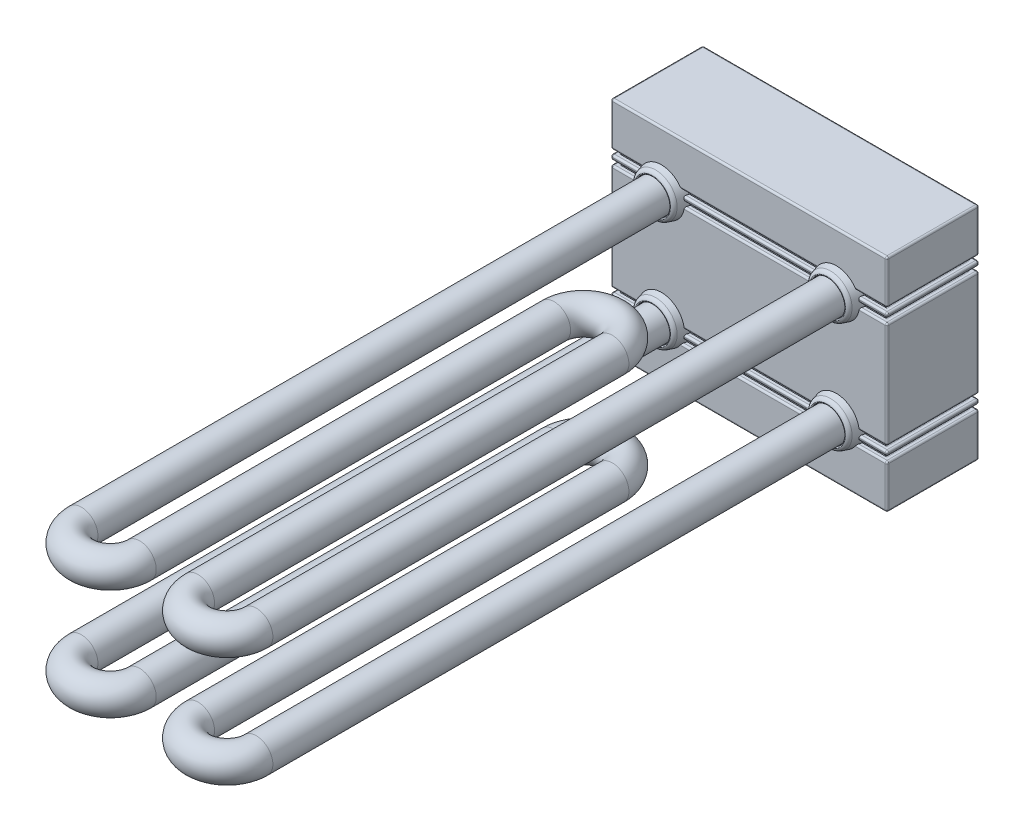
SolidWorks part; units mm, degrees
ref_plane "Front Plane" through (0, 0, 0) normal (0, 0, 1) x (1, 0, 0)
ref_plane "Top Plane" through (0, 0, 0) normal (0, 1, 0) x (1, 0, 0)
ref_plane "Right Plane" through (0, 0, 0) normal (1, 0, 0) x (0, 0, -1)
sketch "Sketch1" plane through (0, 0, 0) normal (0, 0, 1) x (1, 0, 0)
  line L1 (-19.05, -15.24) -> (19.05, -15.24)
  line L2 (-19.05, -15.24) -> (-19.05, 15.24)
  line L3 (-19.05, 15.24) -> (19.05, 15.24)
  line L4 (19.05, -15.24) -> (19.05, 15.24)
  line L5 (-19.05, -15.24) -> (19.05, 15.24) construction
  line L6 (-19.05, 15.24) -> (19.05, -15.24) construction
  point P0 (0, 0)
  dimension "D1" = 30.48
  dimension "D2" = 38.1
extrude "Boss-Extrude1" add sketch "Sketch1" along normal blind 12.7
ref_plane "Plane1" through (0, 8.89, 0) normal (0, 1, 0) x (1, 0, 0)
sketch "Sketch2" plane through (0, 8.89, 0) normal (0, 1, 0) x (1, 0, 0)
  line L1 (-19.05, -12.7) -> (19.05, -12.7)
  line L2 (-19.05, -12.7) -> (-19.05, 0)
  line L3 (-19.05, 0) -> (19.05, 0)
  line L4 (19.05, -12.7) -> (19.05, 0)
  line L5 (-18.161, -12.065) -> (18.161, -12.065)
  line L6 (-18.161, -12.065) -> (-18.161, -0.635)
  line L7 (-18.161, -0.635) -> (18.161, -0.635)
  line L8 (18.161, -12.065) -> (18.161, -0.635)
  dimension "D1" = 0.635
  dimension "D2" = 0.635
  dimension "D3" = 0.889
  dimension "D4" = 0.889
extrude "Cut-Extrude1" cut sketch "Sketch2" against normal mid plane 0.635
pattern_linear "LPattern1" count 2 spacing 1.27 along (0, -1, 0) of "Cut-Extrude1"
mirror "Mirror1" about plane through (0, 0, 0) normal (0, 1, 0) of "LPattern1", "Cut-Extrude1"
fillet "Fillet1" radius 0.254 92 edges at (-18.161, 8.5725, 6.35) (-18.161, 9.2075, 6.35) (18.161, 8.5725, 6.35) (18.161, 9.2075, 6.35) (-18.161, 7.3025, 6.35) (-18.161, 7.9375, 6.35) (18.161, 7.3025, 6.35) (18.161, 7.9375, 6.35) (18.161, -7.3025, 6.35) (18.161, -7.9375, 6.35) (-18.161, -7.3025, 6.35) (-18.161, -7.9375, 6.35) (18.161, -8.5725, 6.35) (18.161, -9.2075, 6.35) (-18.161, -8.5725, 6.35) (-18.161, -9.2075, 6.35) (-18.161, 8.89, 0.635) (0, 8.5725, 0.635) (18.161, 8.89, 0.635) (0, 9.2075, 0.635) (-18.161, 7.62, 0.635) (0, 7.3025, 0.635) (18.161, 7.62, 0.635) (0, 7.9375, 0.635) (18.161, -7.62, 0.635) (0, -7.3025, 0.635) (-18.161, -7.62, 0.635) (0, -7.9375, 0.635) (18.161, -8.89, 0.635) (0, -8.5725, 0.635) (-18.161, -8.89, 0.635) (0, -9.2075, 0.635) (0, 9.2075, 0) (0, 8.5725, 0) (0, 7.9375, 0) (-19.05, 12.2237, 0) (-19.05, 9.2075, 6.35) (-19.05, 8.255, 0) (-19.05, 8.5725, 6.35) (-19.05, 7.9375, 6.35) (19.05, 12.2237, 0) (19.05, 9.2075, 6.35) (-19.05, 12.2237, 12.7) (19.05, 12.2237, 12.7) (0, 9.2075, 12.7) (19.05, 8.5725, 6.35) (19.05, 8.255, 0) (19.05, 7.9375, 6.35) (-19.05, 8.255, 12.7) (0, 8.5725, 12.7) (19.05, 8.255, 12.7) (0, 7.9375, 12.7) (0, -8.5725, 12.7) (0, -7.9375, 12.7) (0, -8.5725, 0) (0, -7.9375, 0) (-19.05, -8.255, 12.7) (-19.05, -8.5725, 6.35) (-19.05, -8.255, 0) (-19.05, -7.9375, 6.35) (0, -9.2075, 0) (-19.05, -12.2237, 0) (-19.05, -9.2075, 6.35) (19.05, -8.255, 0) (19.05, -8.5725, 6.35) (19.05, -8.255, 12.7) (19.05, -7.9375, 6.35) (19.05, -12.2237, 0) (19.05, -9.2075, 6.35) (19.05, -12.2237, 12.7) (-19.05, -12.2237, 12.7) (0, -9.2075, 12.7) (19.05, 7.3025, 6.35) (19.05, -7.3025, 6.35) (19.05, 0, 0) (0, 7.3025, 0) (0, -7.3025, 0) (-19.05, 7.3025, 6.35) (-19.05, -7.3025, 6.35) (-19.05, 0, 0) (0, 7.3025, 12.7) (19.05, 0, 12.7) (0, -7.3025, 12.7) (-19.05, 0, 12.7) (19.05, 15.24, 6.35) (0, 15.24, 12.7) (-19.05, 15.24, 6.35) (0, 15.24, 0) (-19.05, -15.24, 6.35) (0, -15.24, 12.7) (19.05, -15.24, 6.35) (0, -15.24, 0)
sketch "Sketch3" plane through (0, 0, 12.7) normal (0, 0, 1) x (1, 0, 0)
  line L0 (-18.796, 0) -> (18.796, 0) construction
  line L1 (-18.796, 7.0485) -> (-18.796, -7.0485) construction
  line L2 (18.796, -7.0485) -> (18.796, 7.0485) construction
  line L4 (-12.065, -7.62) -> (12.065, -7.62) construction
  line L5 (-12.065, -7.62) -> (-12.065, 7.62) construction
  line L6 (-12.065, 7.62) -> (12.065, 7.62) construction
  line L7 (12.065, -7.62) -> (12.065, 7.62) construction
  line L8 (-12.065, -7.62) -> (12.065, 7.62) construction
  line L9 (-12.065, 7.62) -> (12.065, -7.62) construction
  circle A0 centre (-12.065, 7.62) radius 3.175
  circle A1 centre (12.065, 7.62) radius 3.175
  circle A2 centre (12.065, -7.62) radius 3.175
  circle A3 centre (-12.065, -7.62) radius 3.175
  point P6 (0, 0)
  dimension "D1" = 6.35
  dimension "D2" = 15.24
  dimension "D3" = 24.13
extrude "Boss-Extrude2" add sketch "Sketch3" against normal blind 1.27 draft 15 and the other way blind 1.27 draft 15 draft outward yes
fillet "Fillet2" radius 0.635 4 edges at (14.8997, -7.62, 13.97) (-9.2303, -7.62, 13.97) (14.8997, 7.62, 13.97) (-9.2303, 7.62, 13.97)
sketch "Sketch4" plane through (0, 0, 13.97) normal (0, 0, 1) x (1, 0, 0)
  circle A0 centre (-12.065, 7.62) radius 2.3475
  circle A1 centre (-12.065, -7.62) radius 2.3475
  circle A2 centre (12.065, 7.62) radius 2.3475
  circle A3 centre (12.065, -7.62) radius 2.3475
  circle A4 centre (-12.065, -7.62) radius 2.3475 construction
  circle A5 centre (-12.065, 7.62) radius 2.3475 construction
  circle A6 centre (12.065, 7.62) radius 2.3475 construction
  circle A7 centre (12.065, -7.62) radius 2.3475 construction
extrude "Cut-Extrude2" cut sketch "Sketch4" against normal blind 6.35
fillet "Fillet3" radius 0.127 4 edges at (14.4125, -7.62, 13.97) (-9.7175, -7.62, 13.97) (14.4125, 7.62, 13.97) (-9.7175, 7.62, 13.97)
sketch "Sketch5" plane through (0, 0, 7.62) normal (0, 0, 1) x (1, 0, 0)
  circle A0 centre (-12.065, 7.62) radius 2.284
  circle A1 centre (-12.065, 7.62) radius 2.3475 construction
  circle A2 centre (-12.065, -7.62) radius 2.284
  circle A3 centre (-12.065, -7.62) radius 2.3475 construction
  circle A4 centre (12.065, 7.62) radius 2.284 construction
  dimension "D1" = 0.0635
ref_plane "Plane2" through (0, 7.62, 0) normal (0, 1, 0) x (1, 0, 0)
sketch "Sketch6" plane through (0, 7.62, 0) normal (0, 1, 0) x (1, 0, 0)
  line L0 (-12.065, -7.62) -> (-12.065, -102.87) construction
  line L1 (-14.349, -7.62) -> (-9.781, -7.62) construction
  line L2 (-18.796, 0) -> (18.796, 0) construction
  line L3 (-12.065, -7.62) -> (-12.065, -92.71)
  line L4 (-4.0217, -92.71) -> (-4.0217, -35.56)
  line L5 (0, -35.56) -> (0, 0) construction
  line L6 (12.065, -7.62) -> (12.065, -102.87) construction
  line L7 (4.0217, -92.71) -> (4.0217, -35.56)
  line L8 (12.065, -7.62) -> (12.065, -92.71)
  arc A0 (-12.065, -92.71) -> (-4.0217, -92.71) centre (-8.0433, -92.71) ccw
  arc A1 (-4.0217, -35.56) -> (4.0217, -35.56) centre (0, -35.56) cw
  arc A2 (12.065, -92.71) -> (4.0217, -92.71) centre (8.0433, -92.71) cw
  dimension "D2" = 10.16
  dimension "D1" = 102.87
  dimension "D3" = 57.15
sweep "Sweep1" add profiles "Sketch5" path "Sketch6"
